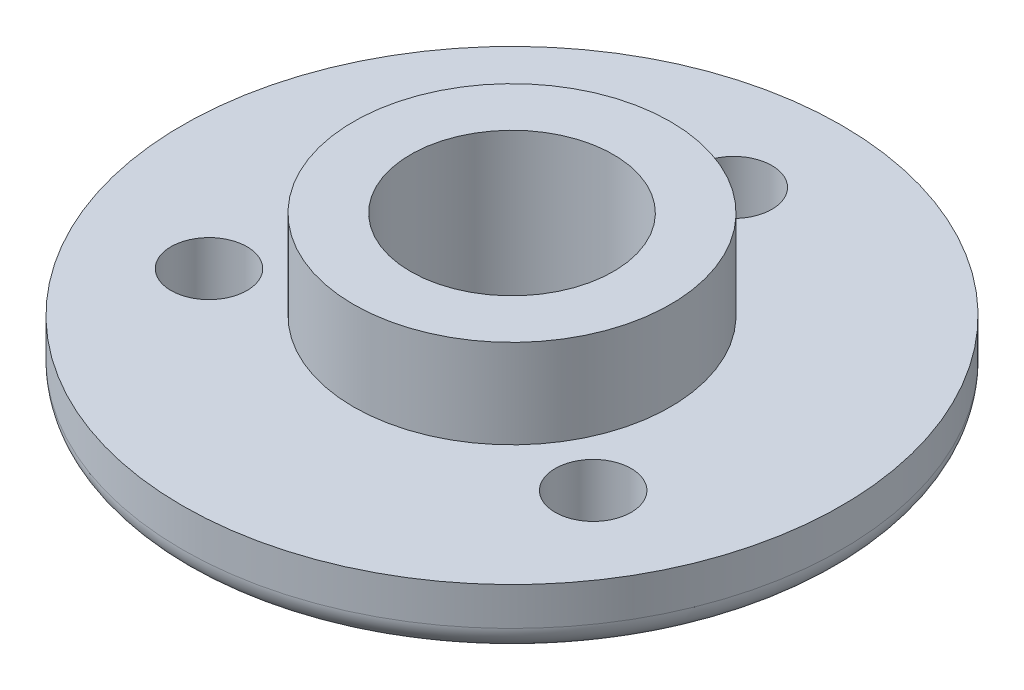
SolidWorks part; units mm, degrees
material "Plain Carbon Steel"
ref_plane "Front Plane" through (0, 0, 0) normal (0, 0, 1) x (1, 0, 0)
ref_plane "Top Plane" through (0, 0, 0) normal (0, 1, 0) x (1, 0, 0)
ref_plane "Right Plane" through (0, 0, 0) normal (1, 0, 0) x (0, 0, -1)
sketch "Sketch1" plane through (0, 0, 0) normal (0, 1, 0) x (1, 0, 0)
  line L0 (0, 30.3136) -> (0, -29.9311) construction
  line L1 (-30.0267, 0) -> (34.808, 0) construction
  circle A0 centre (0, 0) radius 26
  circle A1 centre (0, 0) radius 8
  circle A2 centre (0, 0) radius 12.5
  circle A3 centre (0, 0) radius 17.5 construction
  circle A4 centre (0, 17.5) radius 3
  circle A5 centre (15.1554, -8.75) radius 3
  circle A6 centre (-15.1554, -8.75) radius 3
  point P19 (0, 0)
  dimension "D1" = 52
  dimension "D2" = 25
  dimension "D3" = 16
  dimension "D4" = 35
  dimension "D5" = 6
  dimension "D6" = 3
extrude "Boss-Extrude1" add sketch "Sketch1" along normal blind 5 contours A0
extrude "Cut-Extrude1" cut sketch "Sketch1<3>" along normal through all both and the other way through all contours A6 | A5 | A4
sketch "Sketch1<3>" plane through (0, 0, 0) normal (0, 1, 0) x (1, 0, 0) same geometry as "Sketch1"
extrude "Boss-Extrude2" add sketch "Sketch1<4>" along normal blind 12 contours A2
sketch "Sketch1<4>" plane through (0, 0, 0) normal (0, 1, 0) x (1, 0, 0) same geometry as "Sketch1"
extrude "Cut-Extrude2" cut sketch "Sketch1<5>" along normal through all both and the other way through all contours A1
sketch "Sketch1<5>" plane through (0, 0, 0) normal (0, 1, 0) x (1, 0, 0) same geometry as "Sketch1"
fillet "Fillet1" radius 2 1 edges at (0, 0, 26)
